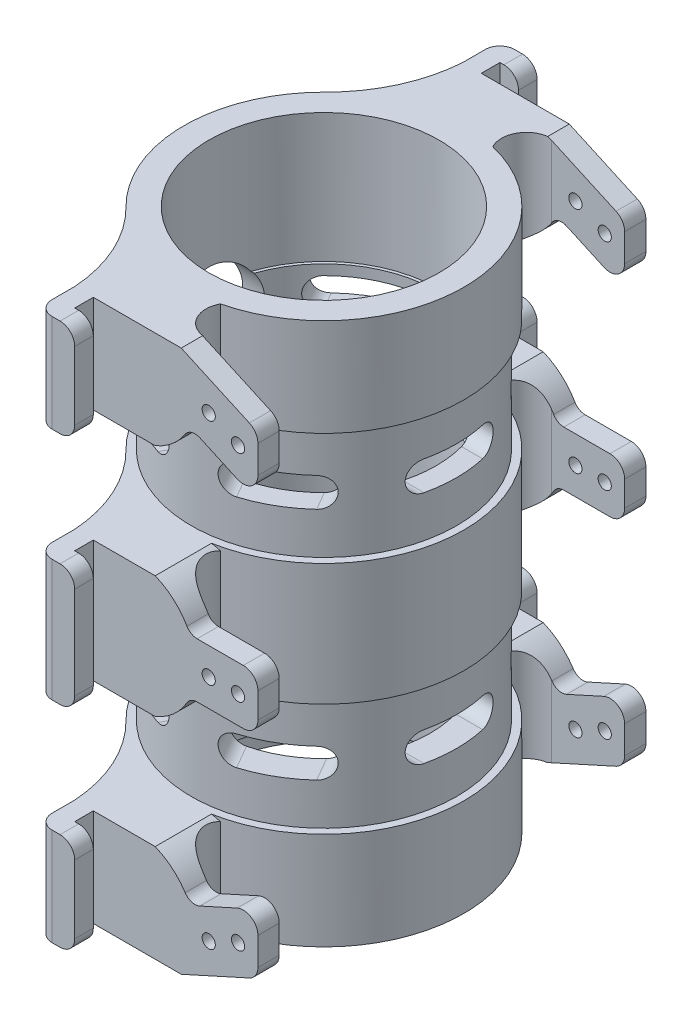
SolidWorks part; units mm, degrees
ref_plane "Front Plane" through (0, 0, 0) normal (0, 0, 1) x (1, 0, 0)
ref_plane "Top Plane" through (0, 0, 0) normal (0, 1, 0) x (1, 0, 0)
ref_plane "Right Plane" through (0, 0, 0) normal (1, 0, 0) x (0, 0, -1)
sketch "Sketch1" plane through (0, 0, 0) normal (0, 1, 0) x (1, 0, 0)
  line L0 (0, 38.25) -> (0, 45.25) construction
  circle A0 centre (0, 0) radius 38.25
  circle A1 centre (0, 0) radius 45.25
  dimension "D1" = 76.5
  dimension "D2" = 7
extrude "Boss-Extrude1" add sketch "Sketch1" along normal mid plane 185
sketch "Sketch2" plane through (0, -92.5, 0) normal (0, -1, 0) x (1, 0, 0)
  line L0 (0, 36.25) -> (0, 38.25) construction
  circle A0 centre (0, 0) radius 36.25
  circle A1 centre (0, 0) radius 38.25 construction
  circle A2 centre (0, 0) radius 38.25
  dimension "D1" = 2
extrude "Boss-Extrude2" add sketch "Sketch2" against normal blind 100 from offset 6.35 offset against normal yes
sketch "Sketch6" plane through (0, 92.5, 0) normal (0, 1, 0) x (1, 0, 0)
  line L0 (0, 38.25) -> (0, 39.25) construction
  circle A0 centre (0, 0) radius 39.25
  circle A1 centre (0, 0) radius 38.25 construction
  circle A2 centre (0, 0) radius 38.25
  dimension "D1" = 1
extrude "Cut-Extrude3" cut sketch "Sketch6" against normal blind 44
sketch "Sketch7" plane through (0, 0, 0) normal (1, 0, 0) x (0, 0, -1)
  line L0 (45.25, 92.5) -> (-45.25, 92.5) construction
  circle A0 centre (0, 40) radius 15
  dimension "D2" = 30
  dimension "D1" = 52.5
extrude "Cut-Extrude4" cut sketch "Sketch7" against normal through all
sketch "Sketch8" plane through (0, 0, 0) normal (0, 1, 0) x (1, 0, 0)
  line L1 (17.5, -66.175) -> (128.1882, -66.175) construction
  line L2 (-18.85, -66.175) -> (-18.85, -78.875)
  line L3 (-18.85, -78.875) -> (-6.15, -78.875)
  line L4 (45.25, 0) -> (-45.25, 0) construction
  line L5 (31.75, 0) -> (50, 0) construction
  line L6 (-6.15, -78.875) -> (-6.15, -72.525)
  line L7 (-12.5, -72.525) -> (17.5, -72.525) construction
  line L8 (-6.15, -72.525) -> (-12.5, -72.525)
  line L9 (-12.5, -72.525) -> (-12.5, -66.175)
  line L10 (-12.5, -66.175) -> (43.65, -66.175)
  line L11 (-12.5, 66.175) -> (43.65, 66.175)
  line L12 (-12.5, 72.525) -> (-12.5, 66.175)
  line L13 (-6.15, 72.525) -> (-12.5, 72.525)
  line L14 (-6.15, 78.875) -> (-6.15, 72.525)
  line L15 (-18.85, 78.875) -> (-6.15, 78.875)
  line L16 (-18.85, 66.175) -> (-18.85, 78.875)
  line L18 (43.65, -66.175) -> (43.65, -58.9107)
  line L19 (43.65, -58.9107) -> (18.65, -58.9107)
  line L20 (43.65, 58.9107) -> (18.65, 58.9107)
  line L21 (43.65, 66.175) -> (43.65, 58.9107)
  line L22 (-12.5, -72.525) -> (-18.85, -72.525) construction
  arc A0 (-32.8241, -31.1471) -> (-18.85, -66.175) centre (-69.7381, -66.175) cw
  circle A1 centre (0, 0) radius 45.25 construction
  arc A2 (-32.8241, -31.1471) -> (15.7007, -42.4388) centre (0, 0) ccw
  arc A3 (-32.8241, 31.1471) -> (15.7007, 42.4388) centre (0, 0) cw
  arc A4 (-32.8241, 31.1471) -> (-18.85, 66.175) centre (-69.7381, 66.175) ccw
  arc A9 (18.65, -58.9107) -> (15.7007, -42.4388) centre (18.65, -50.4107) cw
  arc A10 (18.65, 58.9107) -> (15.7007, 42.4388) centre (18.65, 50.4107) ccw
  dimension "D1" = 8.5
  dimension "D2" = 62.5
  dimension "D3" = 25
extrude "Boss-Extrude3" add sketch "Sketch8" along normal up to surface and the other way up to surface up to face at (0, 92.5, 39.25) other way up to face at (0, -92.5, 45.25)
sketch "Sketch10" plane through (0, 0, 66.175) normal (0, 0, 1) x (1, 0, 0)
  line L0 (17.5, -92.5) -> (43.65, -92.5)
  line L1 (43.65, -92.5) -> (43.65, -80.6536)
  line L2 (-6.15, -59.2129) -> (-32.8241, -59.2129)
  line L3 (128.1882, -42.3564) -> (17.5, -92.5) construction
  line L4 (43.65, -80.6536) -> (17.5, -92.5)
  line L5 (43.65, 80.6536) -> (43.65, 92.5)
  line L6 (17.5, 92.5) -> (128.1882, 42.3564) construction
  line L7 (43.65, 92.5) -> (17.5, 92.5)
  line L8 (-12.5, 92.5) -> (43.65, 92.5) construction
  line L9 (17.5, 92.5) -> (43.65, 80.6536)
  line L10 (43.65, -60.1882) -> (43.65, -9.3209)
  line L11 (79.953, -43.7423) -> (23.8431, -69.161) construction
  line L12 (22.9086, -9.3209) -> (60.2886, -9.3209) construction
  line L21 (22.9086, -9.3209) -> (43.65, -9.3209)
  line L23 (43.65, -60.1882) -> (23.8431, -69.161)
  line L25 (-6.15, 92.5) -> (-6.15, -92.5) construction
  line L26 (-32.8241, 92.5) -> (-32.8241, -92.5) construction
  line L32 (-32.8241, -59.2129) -> (-32.8241, -20.7871)
  line L36 (-32.8241, -20.7871) -> (-6.15, -20.7871)
  line L40 (0, 0) -> (-32.8241, 0) construction
  line L45 (8.611, -59.2129) -> (-6.15, -59.2129)
  line L46 (8.611, -20.7871) -> (-6.15, -20.7871)
  line L47 (-32.8241, 59.2129) -> (-32.8241, 20.7871)
  line L48 (-6.15, 59.2129) -> (-32.8241, 59.2129)
  line L49 (8.611, 59.2129) -> (-6.15, 59.2129)
  line L50 (43.65, 60.1882) -> (23.8431, 69.161)
  line L51 (43.65, 60.1882) -> (43.65, 9.3209)
  line L52 (22.9086, 9.3209) -> (43.65, 9.3209)
  line L53 (8.611, 20.7871) -> (-6.15, 20.7871)
  line L54 (-32.8241, 20.7871) -> (-6.15, 20.7871)
  line L55 (43.65, 92.5) -> (43.65, -92.5) construction
  arc A6 (18.8427, -67.7035) -> (23.8431, -69.161) centre (22.1925, -65.5175) ccw construction
  arc A7 (18.8427, -67.7035) -> (8.611, -59.2129) centre (0, -80) ccw construction
  arc A10 (8.611, -20.7871) -> (19.4507, -11.3102) centre (0, 0) ccw construction
  arc A11 (22.9086, -9.3209) -> (19.4507, -11.3102) centre (22.9086, -13.3209) ccw construction
  arc A18 (18.8427, -67.7035) -> (23.8431, -69.161) centre (22.1925, -65.5175) ccw
  arc A19 (18.8427, -67.7035) -> (8.611, -59.2129) centre (0, -80) ccw
  arc A22 (8.611, -20.7871) -> (19.4507, -11.3102) centre (0, 0) ccw
  arc A23 (22.9086, -9.3209) -> (19.4507, -11.3102) centre (22.9086, -13.3209) ccw
  arc A24 (18.8427, 67.7035) -> (8.611, 59.2129) centre (0, 80) cw
  arc A25 (18.8427, 67.7035) -> (23.8431, 69.161) centre (22.1925, 65.5175) cw
  arc A26 (22.9086, 9.3209) -> (19.4507, 11.3102) centre (22.9086, 13.3209) cw
  arc A27 (8.611, 20.7871) -> (19.4507, 11.3102) centre (0, 0) cw
extrude "Cut-Extrude6" cut sketch "Sketch10" against normal up to surface and the other way through all up to face at (-45.1776, 54.7802, 2.5586)
sketch "Sketch11" plane through (0, 0, -78.875) normal (0, 0, -1) x (-1, 0, 0)
  line L3 (-43.65, 92.5) -> (-43.65, 80.6536)
  line L4 (-17.5, 92.5) -> (-43.65, 92.5)
  line L5 (-43.65, 80.6536) -> (-17.5, 92.5)
  line L6 (-43.65, 92.5) -> (-43.65, 80.6536)
  line L7 (-17.5, 92.5) -> (-43.65, 92.5)
  line L8 (-43.65, 80.6536) -> (-17.5, 92.5)
  line L9 (-43.65, -92.5) -> (-17.5, -92.5)
  line L10 (-43.65, -80.6536) -> (-43.65, -92.5)
  line L11 (-17.5, -92.5) -> (-43.65, -80.6536)
  line L12 (-43.65, -92.5) -> (-17.5, -92.5)
  line L13 (-43.65, -80.6536) -> (-43.65, -92.5)
  line L14 (-17.5, -92.5) -> (-43.65, -80.6536)
  line L20 (32.8241, 20.7871) -> (32.8241, 59.2129)
  line L21 (6.15, 20.7871) -> (32.8241, 20.7871)
  line L22 (-8.611, 20.7871) -> (6.15, 20.7871)
  line L23 (-43.65, 9.3209) -> (-22.9086, 9.3209)
  line L24 (-43.65, 60.1882) -> (-43.65, 9.3209)
  line L25 (-23.8431, 69.161) -> (-43.65, 60.1882)
  line L26 (6.15, 59.2129) -> (-8.611, 59.2129)
  line L27 (32.8241, 59.2129) -> (6.15, 59.2129)
  line L28 (32.8241, 20.7871) -> (32.8241, 59.2129)
  line L29 (6.15, 20.7871) -> (32.8241, 20.7871)
  line L30 (-8.611, 20.7871) -> (6.15, 20.7871)
  line L31 (-43.65, 9.3209) -> (-22.9086, 9.3209)
  line L32 (-43.65, 60.1882) -> (-43.65, 9.3209)
  line L33 (-23.8431, 69.161) -> (-43.65, 60.1882)
  line L34 (6.15, 59.2129) -> (-8.611, 59.2129)
  line L35 (32.8241, 59.2129) -> (6.15, 59.2129)
  line L36 (-22.9086, -9.3209) -> (-43.65, -9.3209)
  line L37 (-43.65, -9.3209) -> (-43.65, -60.1882)
  line L38 (-43.65, -60.1882) -> (-23.8431, -69.161)
  line L39 (-8.611, -59.2129) -> (6.15, -59.2129)
  line L40 (6.15, -59.2129) -> (32.8241, -59.2129)
  line L41 (32.8241, -59.2129) -> (32.8241, -20.7871)
  line L42 (32.8241, -20.7871) -> (6.15, -20.7871)
  line L43 (6.15, -20.7871) -> (-8.611, -20.7871)
  line L44 (-22.9086, -9.3209) -> (-43.65, -9.3209)
  line L45 (-43.65, -9.3209) -> (-43.65, -60.1882)
  line L46 (-43.65, -60.1882) -> (-23.8431, -69.161)
  line L47 (-8.611, -59.2129) -> (6.15, -59.2129)
  line L48 (6.15, -59.2129) -> (32.8241, -59.2129)
  line L49 (32.8241, -59.2129) -> (32.8241, -20.7871)
  line L50 (32.8241, -20.7871) -> (6.15, -20.7871)
  line L51 (6.15, -20.7871) -> (-8.611, -20.7871)
  arc A4 (-8.611, 20.7871) -> (-19.4507, 11.3102) centre (0, 0) ccw
  arc A5 (-22.9086, 9.3209) -> (-19.4507, 11.3102) centre (-22.9086, 13.3209) ccw
  arc A6 (-18.8427, 67.7035) -> (-23.8431, 69.161) centre (-22.1925, 65.5175) ccw
  arc A7 (-18.8427, 67.7035) -> (-8.611, 59.2129) centre (0, 80) ccw
  arc A8 (-8.611, 20.7871) -> (-19.4507, 11.3102) centre (0, 0) ccw
  arc A9 (-22.9086, 9.3209) -> (-19.4507, 11.3102) centre (-22.9086, 13.3209) ccw
  arc A10 (-18.8427, 67.7035) -> (-23.8431, 69.161) centre (-22.1925, 65.5175) ccw
  arc A11 (-18.8427, 67.7035) -> (-8.611, 59.2129) centre (0, 80) ccw
  arc A12 (-23.8431, -69.161) -> (-18.8427, -67.7035) centre (-22.1925, -65.5175) ccw
  arc A13 (-8.611, -59.2129) -> (-18.8427, -67.7035) centre (0, -80) ccw
  arc A14 (-19.4507, -11.3102) -> (-8.611, -20.7871) centre (0, 0) ccw
  arc A15 (-19.4507, -11.3102) -> (-22.9086, -9.3209) centre (-22.9086, -13.3209) ccw
  arc A16 (-23.8431, -69.161) -> (-18.8427, -67.7035) centre (-22.1925, -65.5175) ccw
  arc A17 (-8.611, -59.2129) -> (-18.8427, -67.7035) centre (0, -80) ccw
  arc A18 (-19.4507, -11.3102) -> (-8.611, -20.7871) centre (0, 0) ccw
  arc A19 (-19.4507, -11.3102) -> (-22.9086, -9.3209) centre (-22.9086, -13.3209) ccw
  dimension "D1" = 0
  dimension "D2" = 0
  dimension "D3" = 0
  dimension "D4" = 0
extrude "Cut-Extrude7" cut sketch "Sketch11" against normal up to surface (66.9486 mm away) up to face at (-3.9052, 0.3336, 17.6166)
fillet "Fillet4" radius 5 24 edges at (43.65, 80.6536, -62.5429) (43.65, 60.1882, -62.5429) (43.65, 9.3209, -62.5429) (43.65, -9.3209, -62.5429) (43.65, -60.1882, -62.5429) (43.65, -80.6536, -62.5429) (43.65, -80.6536, 62.5429) (43.65, -60.1882, 62.5429) (43.65, -9.3209, 62.5429) (43.65, 9.3209, 62.5429) (43.65, 60.1882, 62.5429) (43.65, 80.6536, 62.5429) (-6.15, 92.5, -75.7) (-6.15, 59.2129, -75.7) (-6.15, 20.7871, -75.7) (-6.15, -20.7871, -75.7) (-6.15, -59.2129, -75.7) (-6.15, -92.5, -75.7) (-6.15, -92.5, 75.7) (-6.15, -59.2129, 75.7) (-6.15, -20.7871, 75.7) (-6.15, 20.7871, 75.7) (-6.15, 59.2129, 75.7) (-6.15, 92.5, 75.7)
fillet "Fillet5" radius 5 6 edges at (-18.85, -75.8565, -78.875) (-18.85, 0, -78.875) (-18.85, 75.8565, -78.875) (-18.85, 0, 78.875) (-18.85, -75.8565, 78.875) (-18.85, 75.8565, 78.875)
sketch "Sketch14" plane through (0, 0, -66.175) normal (0, 0, -1) x (-1, 0, 0)
  line L0 (-36.867, 73.4937) -> (-26.867, 78.0239) construction
  line L1 (-17.5, 92.5) -> (-40.7132, 81.984) construction
  line L2 (-40.7132, 81.984) -> (-33.0207, 65.0034) construction
  line L3 (-36.5868, 63.3879) -> (-23.8431, 69.161) construction
  line L4 (0, 0) -> (-36.867, 0) construction
  line L5 (-26.867, 78.0239) -> (-26.867, 0) construction
  circle A2 centre (-36.867, 73.4937) radius 2.25
  circle A3 centre (-26.867, 78.0239) radius 2.25
  circle A4 centre (-36.867, 0) radius 2.25
  circle A5 centre (-26.867, 0) radius 2.25
  circle A6 centre (-36.867, -73.4937) radius 2.25
  circle A7 centre (-26.867, -78.0239) radius 2.25
  point P16 (-36.867, 73.4937)
  dimension "D1" = 4.5
  dimension "D2" = 10
extrude "Cut-Extrude8" cut sketch "Sketch14" against normal up to surface (7.2643 mm away) up to face at (30.7785, -73.3041, -58.9107)
sketch "Sketch15" plane through (0, 0, 66.175) normal (0, 0, 1) x (1, 0, 0)
  circle A1 centre (36.867, -73.4937) radius 2.25
  circle A2 centre (36.867, -73.4937) radius 2.25
  circle A3 centre (36.867, 0) radius 2.25
  circle A4 centre (36.867, 0) radius 2.25
  circle A5 centre (26.867, 78.0239) radius 2.25
  circle A6 centre (26.867, 78.0239) radius 2.25
  circle A7 centre (36.867, 73.4937) radius 2.25
  circle A8 centre (36.867, 73.4937) radius 2.25
  circle A9 centre (26.867, -78.0239) radius 2.25
  circle A10 centre (26.867, -78.0239) radius 2.25
  circle A11 centre (26.867, 0) radius 2.25
  circle A12 centre (26.867, 0) radius 2.25
  dimension "D1" = 0
  dimension "D2" = 0
  dimension "D3" = 0
  dimension "D4" = 0
  dimension "D5" = 0
  dimension "D6" = 0
extrude "Cut-Extrude9" cut sketch "Sketch15" against normal up to surface (7.2643 mm away) up to face at (30.7785, -73.3041, 58.9107)
sketch "Sketch16" plane through (0, 92.5, 0) normal (0, 1, 0) x (1, 0, 0)
  line L0 (-45.25, 0) -> (-47.75, 0) construction
  circle A0 centre (0, 0) radius 47.75
  circle A1 centre (0, 0) radius 45.25
  arc A2 (-32.8241, 31.1471) -> (-32.8241, -31.1471) centre (0, 0) ccw construction
  dimension "D1" = 2.5
extrude "Boss-Extrude4" add sketch "Sketch16" against normal up to surface (33.2871 mm away) up to face at (-11.3824, 59.2129, 65.577)
sketch "Sketch17" plane through (0, -92.5, 0) normal (0, -1, 0) x (1, 0, 0)
  circle A1 centre (0, 0) radius 45.25
  circle A2 centre (0, 0) radius 45.25
  circle A3 centre (0, 0) radius 47.75
  circle A4 centre (0, 0) radius 47.75
  dimension "D1" = 0
  dimension "D2" = 0
extrude "Boss-Extrude5" add sketch "Sketch17" against normal up to surface (33.2871 mm away) up to face at (-11.3824, -59.2129, 65.577)
sketch "Sketch18" plane through (0, -20.7871, 0) normal (0, -1, 0) x (1, 0, 0)
  circle A1 centre (0, 0) radius 47.75
  circle A2 centre (0, 0) radius 47.75
  circle A3 centre (0, 0) radius 45.25
  circle A4 centre (0, 0) radius 45.25
  dimension "D1" = 0
  dimension "D2" = 0
extrude "Boss-Extrude6" add sketch "Sketch18" against normal up to surface (41.5741 mm away) up to face at (-11.3824, 20.7871, 65.577)
sketch "Sketch20" plane through (0, 0, 0) normal (1, 0, 0) x (0, 0, -1)
  line L0 (-45.25, -20.7871) -> (45.25, -20.7871) construction
  line L1 (46.9672, -59.2129) -> (-46.9672, -59.2129) construction
  line L2 (-45.25, 59.2129) -> (45.25, 59.2129) construction
  line L3 (46.9672, 20.7871) -> (-46.9672, 20.7871) construction
  line L4 (-45.25, -20.7871) -> (45.25, -20.7871) construction
  line L5 (46.9672, -59.2129) -> (-46.9672, -59.2129) construction
  line L6 (-45.25, 59.2129) -> (45.25, 59.2129) construction
  line L7 (46.9672, 20.7871) -> (-46.9672, 20.7871) construction
  line L8 (0, -20.7871) -> (0, -59.2129) construction
  line L9 (0, 59.2129) -> (0, 20.7871) construction
  line L10 (-10, 40) -> (10, 40) construction
  line L11 (-10, 45) -> (10, 45)
  line L12 (-10, 35) -> (10, 35)
  line L13 (0, 0) -> (46.4328, 0) construction
  line L14 (46.4328, 19.5496) -> (46.4328, -19.5496) construction
  line L15 (-10, -40) -> (10, -40) construction
  line L16 (-10, -45) -> (10, -45)
  line L17 (-10, -35) -> (10, -35)
  arc A2 (-10, 45) -> (-10, 35) centre (-10, 40) ccw
  arc A3 (10, 35) -> (10, 45) centre (10, 40) ccw
  arc A4 (-10, -45) -> (-10, -35) centre (-10, -40) cw
  arc A5 (10, -35) -> (10, -45) centre (10, -40) cw
  point P2 (0, 40)
  point P14 (0, -20.7871)
  point P30 (0, -40)
  dimension "D1" = 20
  dimension "D2" = 5
extrude "Cut-Extrude10" cut sketch "Sketch20" along normal through all
pattern_circular "CirPattern1" count 6 over 360 about axis through (0, 92.5, 0) along (0, -1, 0) of "Cut-Extrude10" reverse direction yes
ref_plane "Plane1" through (-26.1107, -92.5, 39.9787) normal (0, -1, 0) x (-1, 0, 0)
sketch "Sketch23" plane through (0, -92.5, 0) normal (0, -1, 0) x (1, 0, 0)
  line L0 (0, 0) -> (-47.75, 0) construction
  arc A0 (-18.85, 66.175) -> (-33.5786, 33.9491) centre (-68.7395, 69.4978) cw
  arc A1 (-26.1107, 39.9787) -> (-26.1107, -39.9787) centre (0, 0) ccw construction
  arc A2 (-33.5786, 33.9491) -> (-26.1107, 39.9787) centre (0, 0) cw
  arc A3 (-18.85, 66.175) -> (-26.1107, 39.9787) centre (-69.7381, 66.175) cw
  arc A4 (-18.85, -66.175) -> (-26.1107, -39.9787) centre (-69.7381, -66.175) ccw
  arc A5 (-33.5786, -33.9491) -> (-26.1107, -39.9787) centre (0, 0) ccw
  arc A6 (-18.85, -66.175) -> (-33.5786, -33.9491) centre (-68.7395, -69.4978) ccw
  arc A7 (-26.1107, 39.9787) -> (-18.85, 66.175) centre (-69.7381, 66.175) ccw construction
  dimension "D1" = 50
extrude "Boss-Extrude7" add sketch "Sketch23" against normal up to surface (33.2871 mm away) up to face at (-9.8243, -59.2129, 0)
sketch "Sketch24" plane through (0, 92.5, 0) normal (0, 1, 0) x (1, 0, 0)
  arc A3 (-26.1107, 39.9787) -> (-18.85, 66.175) centre (-69.7381, 66.175) ccw
  arc A4 (-26.1107, 39.9787) -> (-33.5786, 33.9491) centre (0, 0) ccw
  arc A5 (-33.5786, 33.9491) -> (-18.85, 66.175) centre (-68.7395, 69.4978) ccw
  arc A6 (-26.1107, 39.9787) -> (-18.85, 66.175) centre (-69.7381, 66.175) ccw
  arc A7 (-26.1107, 39.9787) -> (-33.5786, 33.9491) centre (0, 0) ccw
  arc A8 (-33.5786, 33.9491) -> (-18.85, 66.175) centre (-68.7395, 69.4978) ccw
  arc A9 (-18.85, -66.175) -> (-33.5786, -33.9491) centre (-68.7395, -69.4978) ccw
  arc A10 (-33.5786, -33.9491) -> (-26.1107, -39.9787) centre (0, 0) ccw
  arc A11 (-18.85, -66.175) -> (-26.1107, -39.9787) centre (-69.7381, -66.175) ccw
  arc A12 (-18.85, -66.175) -> (-33.5786, -33.9491) centre (-68.7395, -69.4978) ccw
  arc A13 (-33.5786, -33.9491) -> (-26.1107, -39.9787) centre (0, 0) ccw
  arc A14 (-18.85, -66.175) -> (-26.1107, -39.9787) centre (-69.7381, -66.175) ccw
  dimension "D1" = 0
  dimension "D2" = 0
extrude "Boss-Extrude8" add sketch "Sketch24" against normal up to surface (33.2871 mm away) up to face at (-45.25, 59.2129, 0)
sketch "Sketch25" plane through (0, 20.7871, 0) normal (0, 1, 0) x (1, 0, 0)
  arc A3 (-18.85, -66.175) -> (-33.5786, -33.9491) centre (-68.7395, -69.4978) ccw
  arc A4 (-33.5786, -33.9491) -> (-26.1107, -39.9787) centre (0, 0) ccw
  arc A5 (-18.85, -66.175) -> (-26.1107, -39.9787) centre (-69.7381, -66.175) ccw
  arc A6 (-18.85, -66.175) -> (-33.5786, -33.9491) centre (-68.7395, -69.4978) ccw
  arc A7 (-33.5786, -33.9491) -> (-26.1107, -39.9787) centre (0, 0) ccw
  arc A8 (-18.85, -66.175) -> (-26.1107, -39.9787) centre (-69.7381, -66.175) ccw
  arc A9 (-26.1107, 39.9787) -> (-18.85, 66.175) centre (-69.7381, 66.175) ccw
  arc A10 (-33.5786, 33.9491) -> (-18.85, 66.175) centre (-68.7395, 69.4978) ccw
  arc A11 (-26.1107, 39.9787) -> (-33.5786, 33.9491) centre (0, 0) ccw
  arc A12 (-26.1107, 39.9787) -> (-18.85, 66.175) centre (-69.7381, 66.175) ccw
  arc A13 (-33.5786, 33.9491) -> (-18.85, 66.175) centre (-68.7395, 69.4978) ccw
  arc A14 (-26.1107, 39.9787) -> (-33.5786, 33.9491) centre (0, 0) ccw
  dimension "D1" = 0
  dimension "D2" = 0
extrude "Boss-Extrude9" add sketch "Sketch25" against normal up to surface (41.5741 mm away) up to face at (-45.25, -20.7871, 0)
